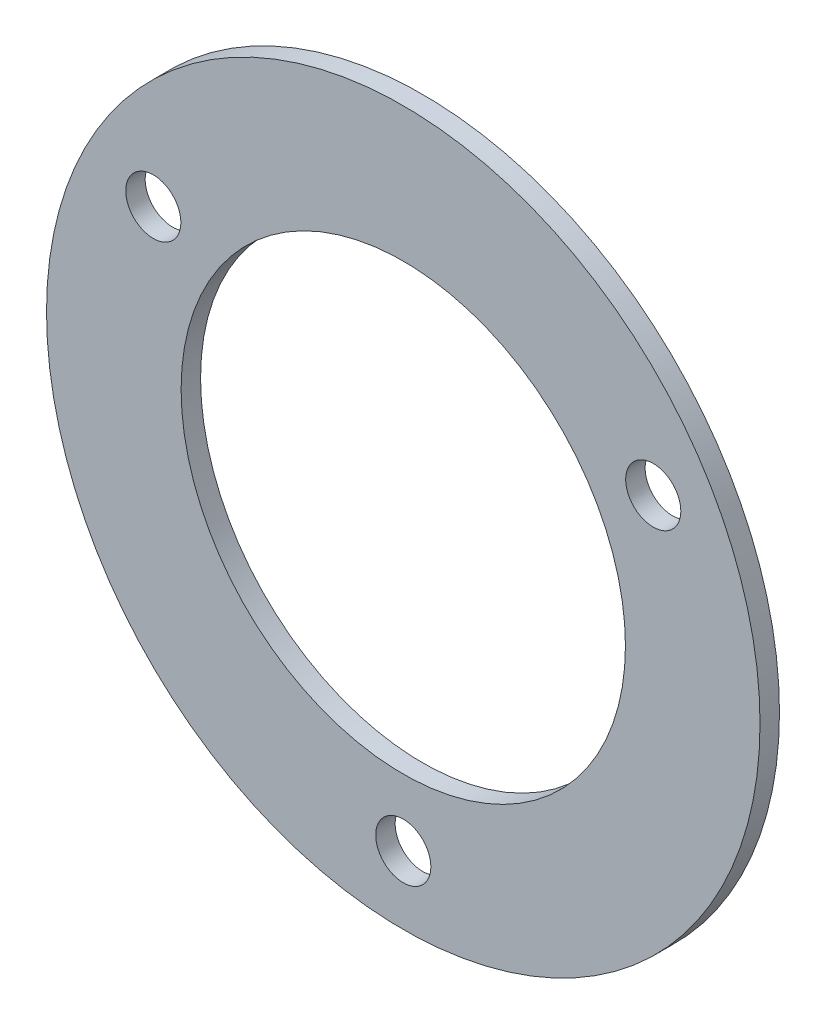
SolidWorks part; units mm, degrees
note: The reader was unsure of these and kept them because the rebuilt part matched: thickness of "Базовая кромка1", "Листовой металл5".
material "AISI 304"
ref_plane "Спереди" through (0, 0, 0) normal (0, 0, 1) x (1, 0, 0)
ref_plane "Сверху" through (0, 0, 0) normal (0, 1, 0) x (1, 0, 0)
ref_plane "Справа" through (0, 0, 0) normal (1, 0, 0) x (0, 0, -1)
sketch "Эскиз1" plane through (0, 0, 0) normal (0, 0, 1) x (1, 0, 0)
  line L0 (77.0763, 44.5) -> (0, 0) construction
  line L1 (0, 89) -> (0, 0) construction
  circle A0 centre (0, 0) radius 110
  circle A1 centre (0, 0) radius 68.5
  circle A2 centre (0, 89) radius 8.5 construction
  circle A3 centre (0, 0) radius 89 construction
  circle A4 centre (77.0763, 44.5) radius 8.5
  circle A5 centre (77.0763, -44.5) radius 8.5 construction
  circle A6 centre (0, -89) radius 8.5
  circle A7 centre (-77.0763, -44.5) radius 8.5 construction
  circle A8 centre (-77.0763, 44.5) radius 8.5
  point P19 (0, 0)
  point P23 (0, 0)
  dimension "D1" = 220
  dimension "D2" = 137
  dimension "D3" = 17
  dimension "D4" = 178
  dimension "D6" = 60
  dimension "D5" = 6
base flange "Базовая кромка1" sketch "Эскиз1" thickness 6 reverse thickness direction no parameters "D1"=4
sketch "Сгиб-Линии1" plane through (0, 0, 0) normal (0, 1, 0) x (1, 0, 0)
sketch "Граничная рамка1" plane through (0, 0, 0) normal (0, 1, 0) x (1, 0, 0)
sheet metal parameters "Листовой металл5" thickness 6 parameters "D1"=4
flat pattern "Развертка5" [suppressed]
sketch "Сгиб-Линии2" plane through (0, 0, 0) normal (0, 1, 0) x (1, 0, 0)
sketch "Граничная рамка2" [suppressed] plane through (0, 0, 0) normal (0, 1, 0) x (1, 0, 0)
